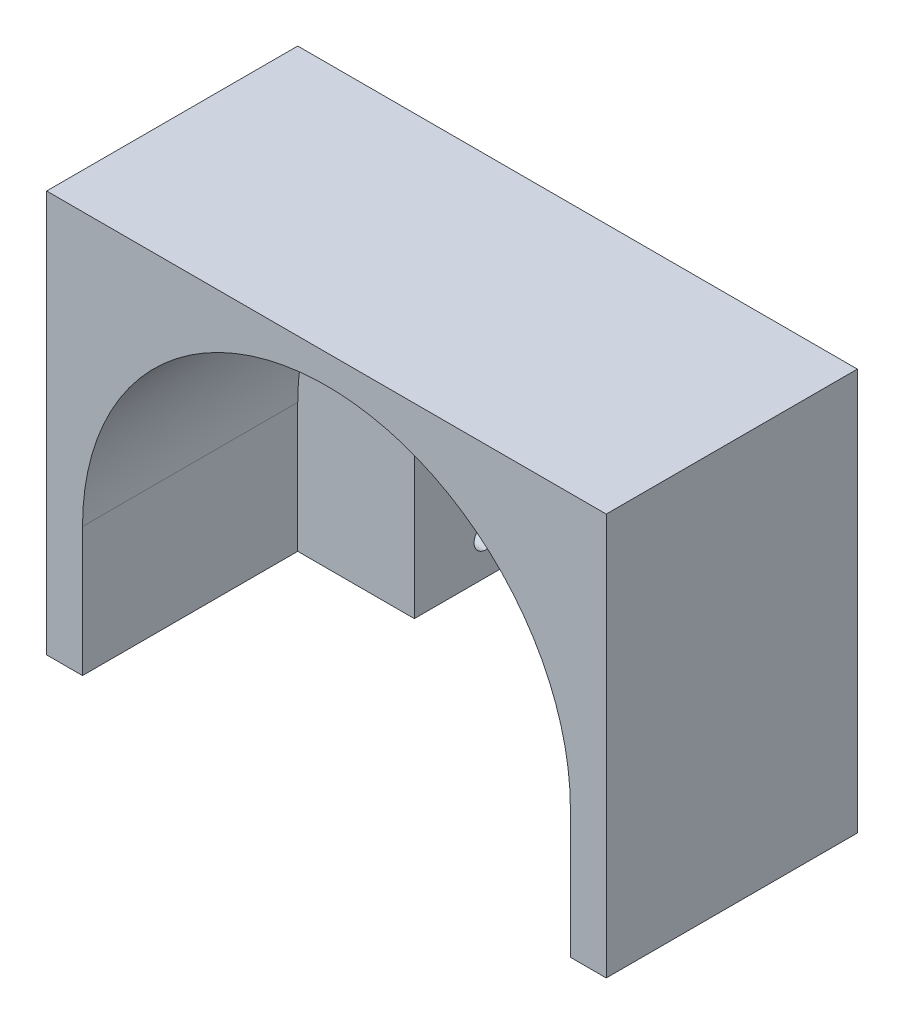
SolidWorks part; units mm, degrees
ref_plane "Plan de face" through (0, 0, 0) normal (0, 0, 1) x (1, 0, 0)
ref_plane "Plan de dessus" through (0, 0, 0) normal (0, 1, 0) x (1, 0, 0)
ref_plane "Plan de droite" through (0, 0, 0) normal (1, 0, 0) x (0, 0, -1)
ref_plane "Plan2" through (0, -10, 0) normal (0, 1, 0) x (1, 0, 0)
sketch "Esquisse3" plane through (0, 0, 0) normal (0, 0, 1) x (1, 0, 0)
  line L1 (-39, 28) -> (39, 28)
  line L2 (-39, 28) -> (-39, -28)
  line L3 (-39, -28) -> (39, -28)
  line L4 (39, 28) -> (39, -28)
  point P4 (0, 28)
  point P5 (-39, 0)
  point P8 (39, 0)
  point P9 (0, -28)
  dimension "D1" = 78
  dimension "D2" = 56
extrude "Boss.-Extru.2" add sketch "Esquisse3" along normal blind 45
sketch "Esquisse4" plane through (0, 0, 45) normal (0, 0, 1) x (1, 0, 0)
  line L2 (39, 28) -> (-39, 28) construction
  line L3 (24.75, -10) -> (-24.75, -10) construction
  circle A0 centre (0, -10) radius 34
  point P2 (0, 28)
  dimension "D1" = 68
extrude "Enlèv. mat.-Extru.1" cut sketch "Esquisse4" against normal blind 30
sketch "Esquisse5" plane through (0, 0, 0) normal (0, 0, -1) x (-1, 0, 0)
  line L0 (39, -28) -> (-39, -28) construction
  line L1 (-17.75, 7.5) -> (17.75, 7.5)
  line L2 (-17.75, 7.5) -> (-17.75, -28)
  line L3 (-17.75, -28) -> (17.75, -28)
  line L4 (17.75, 7.5) -> (17.75, -28)
  point P6 (0, -28)
  dimension "D1" = 35.5
  dimension "D2" = 35.5
extrude "Enlèv. mat.-Extru.2" cut sketch "Esquisse5" against normal up to surface (15 mm away) up to face at (0, -2, 15)
sketch "Esquisse8" plane through (0, 0, 0) normal (0, 0, -1) x (-1, 0, 0)
  line L0 (-22.75, -28) -> (-22.75, 12.5)
  line L1 (-17.75, -28) -> (-39, -28) construction
  line L2 (-22.75, 12.5) -> (22.75, 12.5)
  line L3 (22.75, 12.5) -> (22.75, -28)
  line L4 (39, -28) -> (17.75, -28) construction
  line L5 (22.75, -28) -> (39, -28)
  line L6 (39, -28) -> (39, 28)
  line L7 (39, 28) -> (-39, 28)
  line L8 (-39, 28) -> (-39, -28)
  line L9 (-39, -28) -> (-22.75, -28)
  line L10 (17.75, 7.5) -> (-17.75, 7.5) construction
  line L11 (-17.75, 7.5) -> (-17.75, -28) construction
  line L12 (17.75, -28) -> (17.75, 7.5) construction
  dimension "D1" = 5
  dimension "D2" = 5
  dimension "D3" = 5
extrude "Enlèv. mat.-Extru.5" cut sketch "Esquisse8" against normal blind 10
sketch "Esquisse12" plane through (0, 0, 45) normal (0, 0, 1) x (1, 0, 0)
  line L0 (-39, -28) -> (-28.8444, -28) construction
  line L1 (-34, -28) -> (34, -28)
  line L2 (-34, -28) -> (-34, -10)
  line L3 (-34, -10) -> (34, -10)
  line L4 (34, -28) -> (34, -10)
  line L5 (24.75, -10) -> (-24.75, -10) construction
  arc A0 (28.8444, -28) -> (-28.8444, -28) centre (0, -10) ccw construction
extrude "Enlèv. mat.-Extru.6" cut sketch "Esquisse12" against normal up to surface (30 mm away) up to face at (0, -7.5, 15)
sketch "Esquisse13" plane through (-22.75, 0, 0) normal (-1, 0, 0) x (0, 0, 1)
  line L0 (0, 12.5) -> (0, -28) construction
  line L1 (10, -28) -> (0, -28) construction
  circle A0 centre (5, -23) radius 1.6715
  dimension "D1" = 5
  dimension "D2" = 5
extrude "Enlèv. mat.-Extru.7" cut sketch "Esquisse13" against normal through all
sketch "Esquisse15" plane through (-22.75, 0, 0) normal (-1, 0, 0) x (0, 0, 1)
  line L0 (10, 12.5) -> (0, 12.5) construction
  line L1 (0, 12.5) -> (0, -28) construction
  circle A0 centre (5, 2.5) radius 1.5
  dimension "D1" = 3
  dimension "D2" = 10
  dimension "D3" = 5
extrude "Enlèv. mat.-Extru.8" cut sketch "Esquisse15" against normal through all
sketch "Esquisse16" plane through (0, 0, 15) normal (0, 0, 1) x (1, 0, 0)
  line L0 (-17.75, -28) -> (-17.75, 7.5) construction
  line L1 (-21.75, 3.5) -> (-13.75, 3.5)
  line L2 (-21.75, 3.5) -> (-21.75, 11.5)
  line L3 (-21.75, 11.5) -> (-13.75, 11.5)
  line L4 (-13.75, 3.5) -> (-13.75, 11.5)
  line L6 (-17.75, 7.5) -> (17.75, 7.5) construction
  dimension "D1" = 4
  dimension "D2" = 4
  dimension "D3" = 4
  dimension "D4" = 4
extrude "Enlèv. mat.-Extru.9" cut sketch "Esquisse16" against normal blind 4
sketch "Esquisse17" plane through (0, 12.5, 0) normal (0, 1, 0) x (1, 0, 0)
  line L0 (-22.75, -10) -> (-22.75, 0) construction
  line L1 (22.75, 0) -> (-22.75, 0) construction
  circle A0 centre (-12.75, -5) radius 1.5
  dimension "D1" = 3
  dimension "D2" = 10
  dimension "D3" = 5
extrude "Enlèv. mat.-Extru.10" cut sketch "Esquisse17" against normal through all
sketch "Esquisse18" plane through (0, 12.5, 0) normal (0, 1, 0) x (1, 0, 0)
  line L0 (22.75, -10) -> (22.75, 0) construction
  circle A0 centre (12.75, -5) radius 1.5
  dimension "D1" = 3
  dimension "D2" = 5
  dimension "D3" = 10
extrude "Enlèv. mat.-Extru.11" cut sketch "Esquisse18" against normal through all
sketch "Esquisse19" plane through (0, 0, 15) normal (0, 0, 1) x (1, 0, 0)
  line L0 (17.75, 7.5) -> (17.75, -28) construction
  line L1 (13.75, 11.5) -> (21.75, 11.5)
  line L2 (13.75, 11.5) -> (13.75, 3.5)
  line L3 (13.75, 3.5) -> (21.75, 3.5)
  line L4 (21.75, 11.5) -> (21.75, 3.5)
  line L5 (-13.75, 7.5) -> (17.75, 7.5) construction
  dimension "D1" = 4
  dimension "D2" = 4
  dimension "D3" = 4
  dimension "D4" = 4
extrude "Enlèv. mat.-Extru.12" cut sketch "Esquisse19" against normal blind 4
